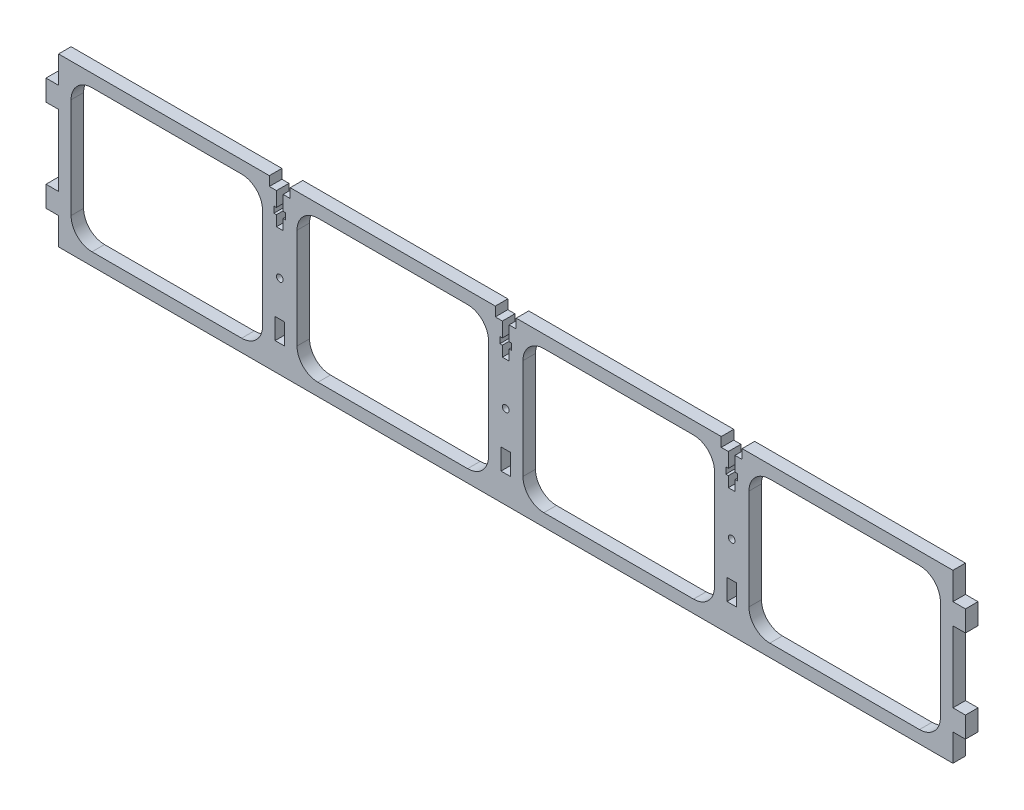
SolidWorks part; units mm, degrees
ref_plane "Front Plane" through (0, 0, 0) normal (0, 0, 1) x (1, 0, 0)
ref_plane "Top Plane" through (0, 0, 0) normal (0, 1, 0) x (1, 0, 0)
ref_plane "Right Plane" through (0, 0, 0) normal (1, 0, 0) x (0, 0, -1)
sketch "Sketch1" plane through (0, 0, 0) normal (0, 0, 1) x (1, 0, 0)
  line L1 (-214, -40) -> (214, -40)
  line L2 (-214, -40) -> (-214, 40)
  line L3 (-214, 40) -> (214, 40)
  line L4 (214, -40) -> (214, 40)
  line L5 (-214, -40) -> (214, 40) construction
  line L6 (-214, 40) -> (214, -40) construction
  point P0 (0, 0)
  dimension "D1" = 428
  dimension "D2" = 80
extrude "Boss-Extrude1" add sketch "Sketch1" along normal blind 6
sketch "Sketch2" plane through (0, 0, 6) normal (0, 0, 1) x (1, 0, 0)
  line L0 (-116.375, -40) -> (-116.375, -27) construction
  line L1 (-208, 40) -> (-208, -40) construction
  line L2 (-214, -34) -> (214, -34) construction
  line L3 (-214, -40) -> (214, -40) construction
  line L8 (214, -40) -> (214, 40)
  line L9 (214, 40) -> (-214, 40)
  line L10 (-214, 40) -> (-214, -40)
  line L11 (-214, -40) -> (214, -40)
  line L12 (214, -40) -> (214, 40) construction
  line L13 (214, 40) -> (-214, 40)
  line L14 (-214, 40) -> (-214, -40) construction
  line L15 (-208, -40) -> (214, -40) construction
  line L16 (-110.375, -40) -> (-110.375, -27) construction
  line L17 (-110.375, -40) -> (-110.375, -27) construction
  line L18 (-116.375, -24) -> (-116.375, 24)
  line L19 (-198, -34) -> (-126.375, -34)
  line L20 (-208, 24) -> (-208, -24)
  line L21 (-126.375, 34) -> (-198, 34)
  arc A0 (-198, 34) -> (-208, 24) centre (-198, 24) ccw
  arc A1 (-126.375, 34) -> (-116.375, 24) centre (-126.375, 24) cw
  arc A2 (-116.375, -24) -> (-126.375, -34) centre (-126.375, -24) cw
  arc A3 (-198, -34) -> (-208, -24) centre (-198, -24) cw
  dimension "D6" = 10
  dimension "D5" = 6
  dimension "D1" = 0
  dimension "D2" = 6
  dimension "D3" = 6
  dimension "D4" = 6
extrude "Cut-Extrude1" cut sketch "Sketch2" against normal up to next contours L18 L21 L20 L19 region at (-162.1875, 0, 6)
pattern_linear "LPattern1" count 4 spacing 108.125 along (1, 0, 0) of "Cut-Extrude1"
sketch "Sketch3" plane through (0, 0, 0) normal (0, 0, -1) x (-1, 0, 0)
  line L8 (-110.375, -27) -> (-110.375, -17) construction
  line L9 (-110.375, -17) -> (-105.875, -17) construction
  line L11 (-105.875, -27) -> (-110.375, -27) construction
  line L24 (-110.375, -27) -> (-110.375, -17)
  line L25 (-110.375, -17) -> (-105.875, -17)
  line L26 (-105.875, -17) -> (-105.875, -27)
  line L27 (-105.875, -27) -> (-110.375, -27)
  line L44 (-2.25, -27) -> (-2.25, -17) construction
  line L45 (-2.25, -17) -> (2.25, -17) construction
  line L46 (2.25, -17) -> (2.25, -27) construction
  line L47 (2.25, -27) -> (-2.25, -27) construction
  line L52 (-2.25, -27) -> (-2.25, -17)
  line L53 (-2.25, -17) -> (2.25, -17)
  line L54 (2.25, -17) -> (2.25, -27)
  line L55 (2.25, -27) -> (-2.25, -27)
  line L60 (105.875, -27) -> (105.875, -17) construction
  line L61 (105.875, -17) -> (110.375, -17) construction
  line L62 (110.375, -17) -> (110.375, -27) construction
  line L63 (110.375, -27) -> (105.875, -27) construction
  line L68 (105.875, -27) -> (105.875, -17)
  line L69 (105.875, -17) -> (110.375, -17)
  line L70 (110.375, -17) -> (110.375, -27)
  line L71 (110.375, -27) -> (105.875, -27)
  circle A3 centre (108.125, 0) radius 1.6 construction
  circle A4 centre (0, 0) radius 1.6 construction
  circle A5 centre (-108.125, 0) radius 1.6 construction
  circle A6 centre (108.125, 0) radius 1.6
  circle A7 centre (0, 0) radius 1.6
  circle A8 centre (-108.125, 0) radius 1.6
extrude "Cut-Extrude2" cut sketch "Sketch3" against normal through all
sketch "Sketch4" plane through (0, 0, 0) normal (0, 0, -1) x (-1, 0, 0)
  line L0 (-111.5, 17) -> (-214, 17) construction
  line L1 (-214, -40) -> (-214, 40) construction
  line L2 (-108.5, 0) -> (-214, 0) construction
  line L3 (-220, 21.3321) -> (-220, 40) construction
  line L4 (-214, 17) -> (-220, 17)
  line L5 (-214, 17) -> (-214, 27)
  line L6 (-214, 27) -> (-220, 27)
  line L7 (-220, 17) -> (-220, 27)
  line L9 (-220, -17) -> (-220, -27)
  line L10 (-214, -27) -> (-220, -27)
  line L11 (-214, -17) -> (-214, -27)
  line L12 (-214, -17) -> (-220, -17)
  line L13 (0, 0) -> (0, 40) construction
  line L14 (-214, 40) -> (214, 40) construction
  line L15 (214, -17) -> (220, -17)
  line L16 (214, -17) -> (214, -27)
  line L17 (214, -27) -> (220, -27)
  line L18 (220, -17) -> (220, -27)
  line L19 (220, 17) -> (220, 27)
  line L20 (214, 27) -> (220, 27)
  line L21 (214, 17) -> (214, 27)
  line L22 (214, 17) -> (220, 17)
  point P13 (-108.5, -1)
  dimension "D1" = 34
  dimension "D2" = 10
extrude "Boss-Extrude2" add sketch "Sketch4" against normal blind 6
sketch "Sketch5" plane through (0, 40, 0) normal (0, 1, 0) x (1, 0, 0)
  line L0 (214, -6) -> (-214, -6) construction
  line L1 (-113.125, 0) -> (-103.125, 0)
  line L2 (-113.125, 0) -> (-113.125, -6)
  line L3 (-113.125, -6) -> (-103.125, -6)
  line L4 (-103.125, 0) -> (-103.125, -6)
  line L5 (-113.125, 0) -> (-103.125, -6) construction
  line L6 (-113.125, -6) -> (-103.125, 0) construction
  line L7 (-103.125, -6) -> (-103.125, 0) construction
  line L8 (5, -6) -> (5, 0) construction
  line L9 (-5, 0) -> (5, 0)
  line L10 (-5, 0) -> (-5, -6)
  line L11 (-5, -6) -> (5, -6)
  line L12 (5, 0) -> (5, -6)
  line L13 (-5, 0) -> (5, -6) construction
  line L14 (-5, -6) -> (5, 0) construction
  line L15 (113.125, -6) -> (113.125, 0) construction
  line L16 (103.125, 0) -> (113.125, 0)
  line L17 (103.125, 0) -> (103.125, -6)
  line L18 (103.125, -6) -> (113.125, -6)
  line L19 (113.125, 0) -> (113.125, -6)
  line L20 (103.125, 0) -> (113.125, -6) construction
  line L21 (103.125, -6) -> (113.125, 0) construction
  point P0 (-108.125, -3)
  point P10 (0, -3)
  point P18 (108.125, -3)
extrude "Cut-Extrude3" cut sketch "Sketch5" against normal blind 4.5
sketch "Sketch6" plane through (0, 0, 0) normal (0, 0, -1) x (-1, 0, 0)
  line L12 (-109.725, 35.5) -> (-109.725, 28.5)
  line L13 (-106.525, 35.5) -> (-109.725, 35.5)
  line L14 (-106.525, 28.5) -> (-106.525, 35.5)
  line L15 (-105.325, 28.5) -> (-106.525, 28.5)
  line L16 (-105.325, 25.5) -> (-105.325, 28.5)
  line L17 (-106.525, 25.5) -> (-105.325, 25.5)
  line L18 (-106.525, 20.5) -> (-106.525, 25.5)
  line L19 (-109.725, 20.5) -> (-106.525, 20.5)
  line L20 (-109.725, 25.5) -> (-109.725, 20.5)
  line L21 (-110.925, 25.5) -> (-109.725, 25.5)
  line L22 (-110.925, 28.5) -> (-110.925, 25.5)
  line L23 (-109.725, 28.5) -> (-110.925, 28.5)
  line L24 (-109.725, 35.5) -> (-109.725, 28.5)
  line L25 (-106.525, 35.5) -> (-109.725, 35.5)
  line L26 (-106.525, 28.5) -> (-106.525, 35.5)
  line L27 (-105.325, 28.5) -> (-106.525, 28.5)
  line L28 (-105.325, 25.5) -> (-105.325, 28.5)
  line L29 (-106.525, 25.5) -> (-105.325, 25.5)
  line L30 (-106.525, 20.5) -> (-106.525, 25.5)
  line L31 (-109.725, 20.5) -> (-106.525, 20.5)
  line L32 (-109.725, 25.5) -> (-109.725, 20.5)
  line L33 (-110.925, 25.5) -> (-109.725, 25.5)
  line L34 (-110.925, 28.5) -> (-110.925, 25.5)
  line L35 (-109.725, 28.5) -> (-110.925, 28.5)
  line L36 (-1.595, 28.5) -> (-2.795, 28.5)
  line L37 (-2.795, 28.5) -> (-2.795, 25.5)
  line L38 (-2.795, 25.5) -> (-1.595, 25.5)
  line L39 (-1.595, 25.5) -> (-1.595, 20.5)
  line L40 (-1.595, 20.5) -> (1.605, 20.5)
  line L41 (1.605, 20.5) -> (1.605, 25.5)
  line L42 (1.605, 25.5) -> (2.805, 25.5)
  line L43 (2.805, 25.5) -> (2.805, 28.5)
  line L44 (2.805, 28.5) -> (1.605, 28.5)
  line L45 (1.605, 28.5) -> (1.605, 35.5)
  line L46 (1.605, 35.5) -> (-1.595, 35.5)
  line L47 (-1.595, 35.5) -> (-1.595, 28.5)
  line L48 (-1.595, 28.5) -> (-2.795, 28.5)
  line L49 (-2.795, 28.5) -> (-2.795, 25.5)
  line L50 (-2.795, 25.5) -> (-1.595, 25.5)
  line L51 (-1.595, 25.5) -> (-1.595, 20.5)
  line L52 (-1.595, 20.5) -> (1.605, 20.5)
  line L53 (1.605, 20.5) -> (1.605, 25.5)
  line L54 (1.605, 25.5) -> (2.805, 25.5)
  line L55 (2.805, 25.5) -> (2.805, 28.5)
  line L56 (2.805, 28.5) -> (1.605, 28.5)
  line L57 (1.605, 28.5) -> (1.605, 35.5)
  line L58 (1.605, 35.5) -> (-1.595, 35.5)
  line L59 (-1.595, 35.5) -> (-1.595, 28.5)
  line L60 (106.535, 35.5) -> (106.535, 28.5)
  line L61 (109.735, 35.5) -> (106.535, 35.5)
  line L62 (109.735, 28.5) -> (109.735, 35.5)
  line L63 (110.935, 28.5) -> (109.735, 28.5)
  line L64 (110.935, 25.5) -> (110.935, 28.5)
  line L65 (109.735, 25.5) -> (110.935, 25.5)
  line L66 (109.735, 20.5) -> (109.735, 25.5)
  line L67 (106.535, 20.5) -> (109.735, 20.5)
  line L68 (106.535, 25.5) -> (106.535, 20.5)
  line L69 (105.335, 25.5) -> (106.535, 25.5)
  line L70 (105.335, 28.5) -> (105.335, 25.5)
  line L71 (106.535, 28.5) -> (105.335, 28.5)
  line L72 (106.535, 35.5) -> (106.535, 28.5)
  line L73 (109.735, 35.5) -> (106.535, 35.5)
  line L74 (109.735, 28.5) -> (109.735, 35.5)
  line L75 (110.935, 28.5) -> (109.735, 28.5)
  line L76 (110.935, 25.5) -> (110.935, 28.5)
  line L77 (109.735, 25.5) -> (110.935, 25.5)
  line L78 (109.735, 20.5) -> (109.735, 25.5)
  line L79 (106.535, 20.5) -> (109.735, 20.5)
  line L80 (106.535, 25.5) -> (106.535, 20.5)
  line L81 (105.335, 25.5) -> (106.535, 25.5)
  line L82 (105.335, 28.5) -> (105.335, 25.5)
  line L83 (106.535, 28.5) -> (105.335, 28.5)
  dimension "D1" = 0
  dimension "D2" = 0
  dimension "D3" = 0
extrude "Cut-Extrude4" cut sketch "Sketch6" against normal up to next
